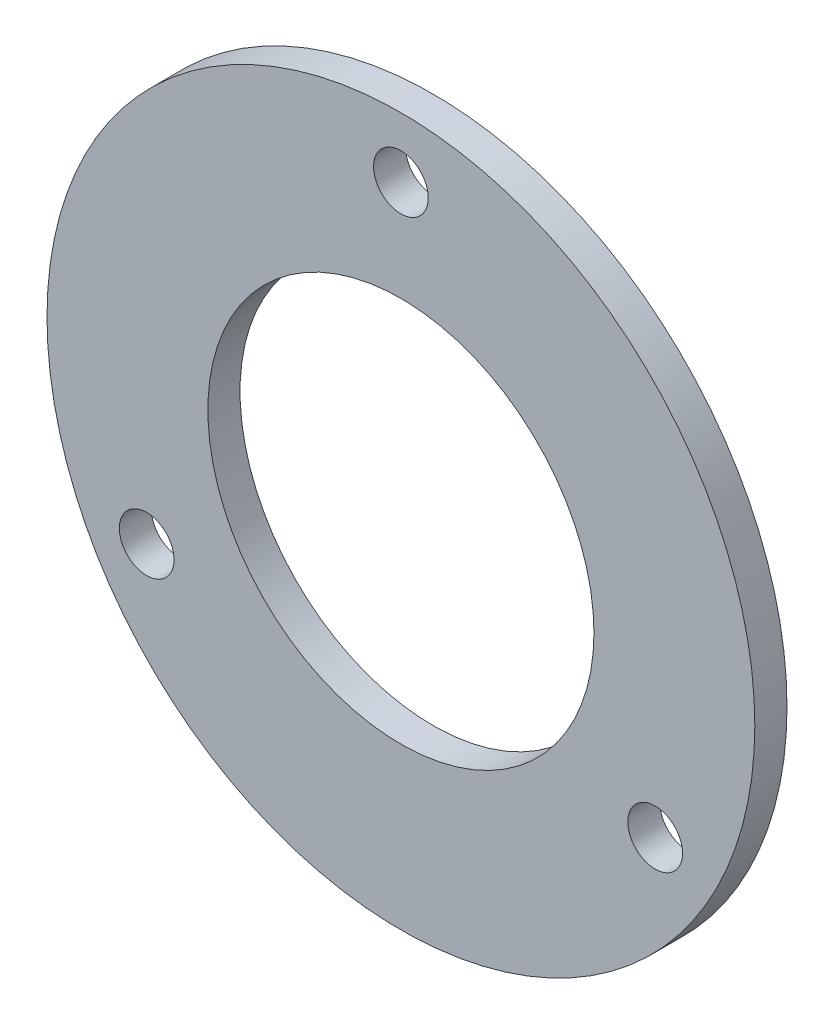
SolidWorks part; units mm, degrees
ref_plane "Front Plane" through (0, 0, 0) normal (0, 0, 1) x (1, 0, 0)
ref_plane "Top Plane" through (0, 0, 0) normal (0, 1, 0) x (1, 0, 0)
ref_plane "Right Plane" through (0, 0, 0) normal (1, 0, 0) x (0, 0, -1)
sketch "S01 - Outer race retaining lip" plane through (0, 0, 0) normal (0, 0, 1) x (1, 0, 0)
  circle A0 centre (0, 0) radius 22
  circle A1 centre (0, 0) radius 12
  dimension "D1" = 24
  dimension "D2" = 44
extrude "01 - Outer race retaining lip" add sketch "S01 - Outer race retaining lip" along normal blind 2
sketch "S02 - Three accessible screw holes" plane through (0, 0, 0) normal (0, 0, 1) x (1, 0, 0)
  circle A0 centre (0, 18.25) radius 1.7
  circle A1 centre (-15.805, -9.125) radius 1.7
  circle A2 centre (15.805, -9.125) radius 1.7
  dimension "D1" = 3.4
  dimension "D2" = 3.4
  dimension "D3" = 3.4
  dimension "D4" = 15.805
  dimension "D5" = 15.805
  dimension "D6" = 18.25
  dimension "D7" = 9.125
extrude "02 - Three accessible screw holes" cut sketch "S02 - Three accessible screw holes" along normal blind 4 from offset 1 offset against normal yes
